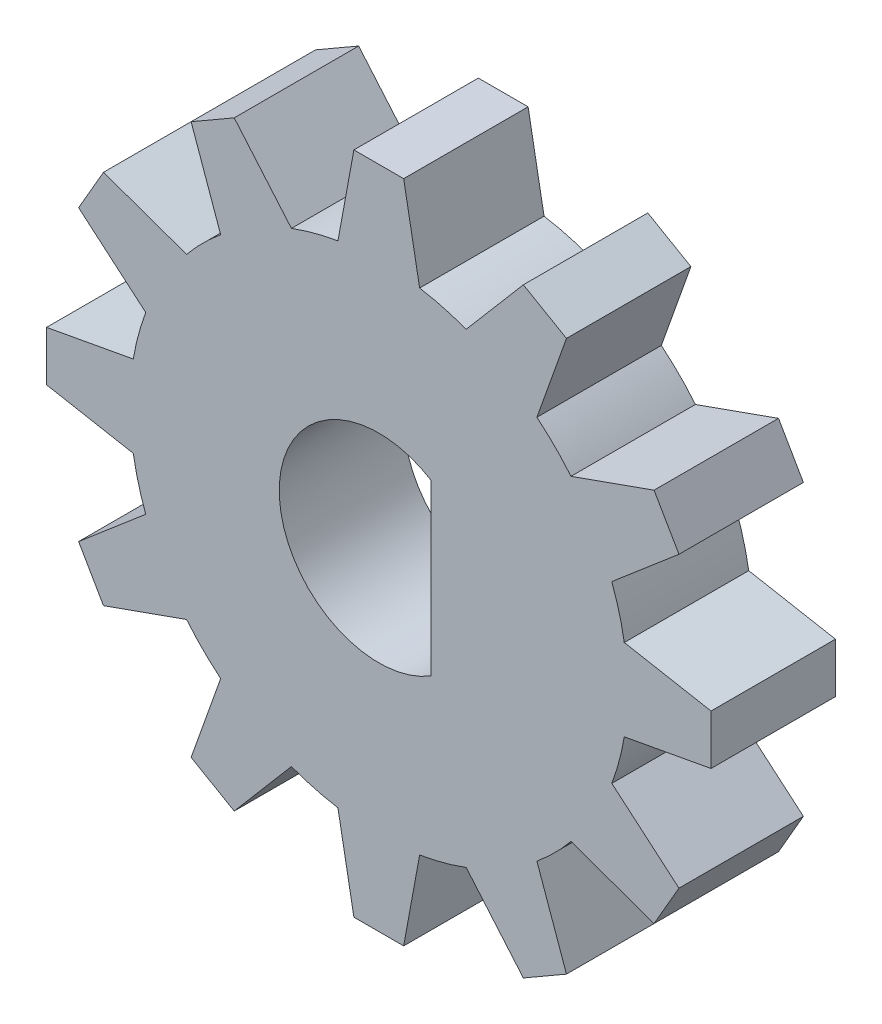
SolidWorks part; units mm, degrees
ref_plane "Front Plane" through (0, 0, 0) normal (0, 0, 1) x (1, 0, 0)
ref_plane "Top Plane" through (0, 0, 0) normal (0, 1, 0) x (1, 0, 0)
ref_plane "Right Plane" through (0, 0, 0) normal (1, 0, 0) x (0, 0, -1)
sketch "Sketch1" plane through (0, 0, 0) normal (0, 0, 1) x (1, 0, 0)
  circle A0 centre (0, 0) radius 10
  dimension "D1" = 20
extrude "Boss-Extrude1" add sketch "Sketch1" along normal blind 5
sketch "Sketch3" plane through (0, 0, 0) normal (0, 0, 1) x (1, 0, 0)
  line L0 (0, -13.35) -> (0, 13.35) construction
  line L1 (-1, 13.35) -> (1, 13.35)
  line L2 (-1, 13.35) -> (-1.8, 9)
  line L3 (-1.8, 9) -> (1.8, 9)
  line L4 (1.8, 9) -> (1, 13.35)
  point P3 (0, 0)
  point P4 (0, 9)
  point P6 (0, 13.35)
  dimension "D1" = 13.35
  dimension "D2" = 3.6
  dimension "D3" = 2
  dimension "D4" = 9
extrude "Boss-Extrude2" add sketch "Sketch3" along normal blind 5
ref_axis "Axis2" through (0, 0, 5) along (0, 0, -1)
pattern_circular "CirPattern1" count 12 every 30 about axis through (0, 0, 0) along (0, 0, 1) of "Boss-Extrude2"
sketch "Sketch4" plane through (0, 0, 0) normal (0, 0, 1) x (1, 0, 0)
  line L0 (2.1, 3.4044) -> (2.1, -3.4044)
  arc A0 (2.1, 3.4044) -> (2.1, -3.4044) centre (0, 0) ccw
  dimension "D1" = 8
  dimension "D2" = 2.1
extrude "Cut-Extrude1" cut sketch "Sketch4" along normal blind 7
sketch "Sketch5" plane through (0, 0, 5) normal (0, 0, 1) x (1, 0, 0)
  circle A0 centre (0, 0) radius 10
  dimension "D1" = 20
